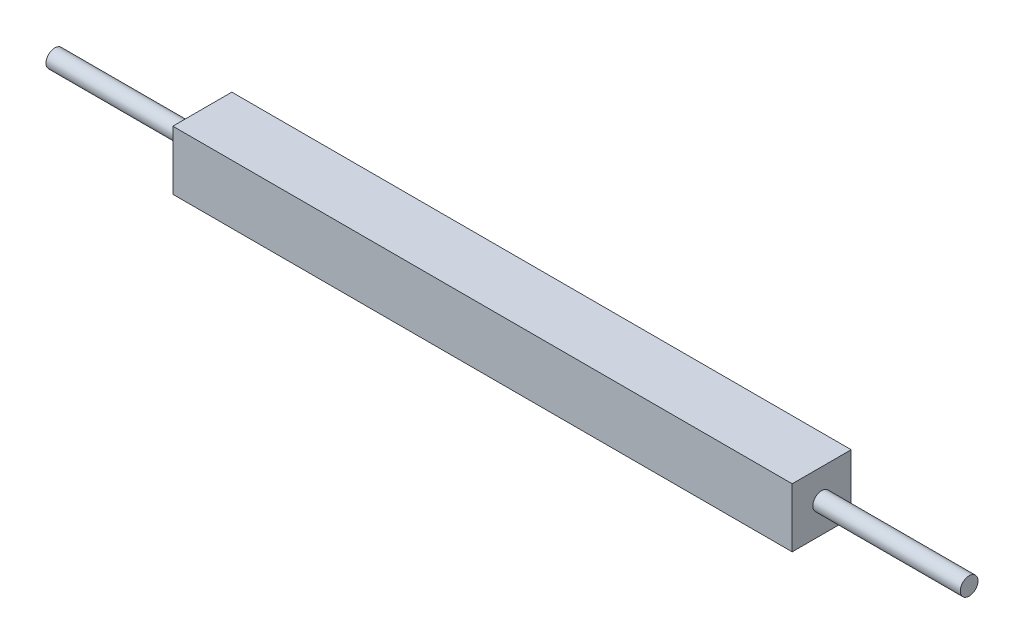
SolidWorks part; units mm, degrees
ref_plane "Front" through (0, 0, 0) normal (0, 0, 1) x (1, 0, 0)
ref_plane "Top" through (0, 0, 0) normal (0, 1, 0) x (1, 0, 0)
ref_plane "Right" through (0, 0, 0) normal (1, 0, 0) x (0, 0, -1)
sketch "Sketch1" plane through (0, 0, 0) normal (0, 0, 1) x (1, 0, 0)
  line L0 (0, 0) -> (0, 20) construction
  line L1 (-210, -20) -> (0, -20)
  line L2 (-210, -20) -> (-210, 20)
  line L3 (-210, 20) -> (0, 20)
  line L5 (-210, -20) -> (0, 0) construction
  line L6 (-210, 20) -> (0, 0) construction
  line L7 (0, 20) -> (0, -20) construction
  line L8 (0, 20) -> (0, -20)
  point P0 (0, 0)
  dimension "D2" = 40
extrude "Boss-Extrude1" add sketch "Sketch1" along normal blind 40
sketch "Sketch2" plane through (-210, 0, 0) normal (-1, 0, 0) x (0, 0, 1)
  line L0 (40, 20) -> (0, -20) construction
  circle A0 centre (20, 0) radius 6
  dimension "D1" = 12
extrude "Boss-Extrude2" add sketch "Sketch2" along normal blind 100
mirror "Mirror1" about plane through (0, 20, 40) normal (-1, 0, 0) of bodies 102
